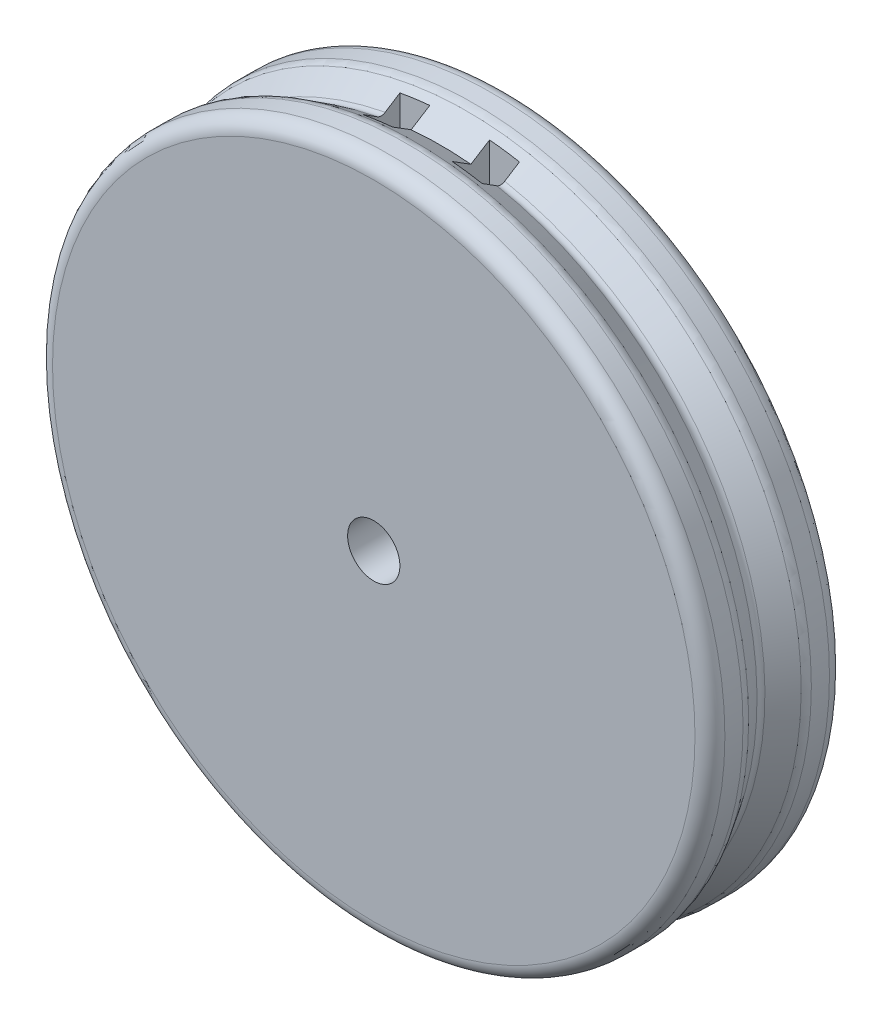
SolidWorks part; units mm, degrees
ref_plane "Front Plane" through (0, 0, 0) normal (0, 0, 1) x (1, 0, 0)
ref_plane "Top Plane" through (0, 0, 0) normal (0, 1, 0) x (1, 0, 0)
ref_plane "Right Plane" through (0, 0, 0) normal (1, 0, 0) x (0, 0, -1)
sketch "Sketch1" plane through (0, 0, 0) normal (0, 0, 1) x (1, 0, 0)
  circle A0 centre (0, 0) radius 42.5
  dimension "D1" = 85
extrude "Boss-Extrude1" add sketch "Sketch1" along normal mid plane 8
sketch "Sketch2" plane through (0, 0, 4) normal (0, 0, 1) x (1, 0, 0)
  circle A0 centre (0, 0) radius 45
  dimension "D1" = 90
extrude "Boss-Extrude2" add sketch "Sketch2" along normal blind 5
sketch "Sketch6" plane through (0, 0, 0) normal (1, 0, 0) x (0, 0, -1)
  line L0 (-4, 45) -> (0, 42.5)
  line L1 (4, 42.5) -> (-4, 42.5) construction
  line L2 (0, 42.5) -> (-4, 42.5)
  line L3 (-4, 42.5) -> (-4, 45)
  line L4 (-30.4204, 0) -> (21.2132, 0) construction
revolve "Revolve1" add sketch "Sketch6" angle 360 about L4
mirror "Mirror1" about plane through (0, 0, 0) normal (0, 0, 1) of "Revolve1", "Boss-Extrude2"
ref_plane "Plane3" through (0, 0, 0) normal (0, 0, 1) x (1, 0, 0)
sketch "Sketch7" plane through (0, 0, 0) normal (0, 0, 1) x (1, 0, 0)
  line L0 (0, 37.5) -> (0, -45) construction
  line L3 (-4, 37.5) -> (-4, 44.8219)
  line L4 (-8, 37.5) -> (-8, 44.2832)
  line L5 (0, 37.5) -> (15.7968, 37.5) construction
  line L6 (4, 37.5) -> (4, 44.8219)
  line L7 (8, 37.5) -> (8, 44.2832)
  arc A2 (-4, 37.5) -> (4, 37.5) centre (0, 37.5) ccw
  arc A3 (-8, 37.5) -> (8, 37.5) centre (0, 37.5) ccw
  circle A6 centre (0, 0) radius 45 construction
  arc A7 (8, 44.2832) -> (4, 44.8219) centre (0, 0) ccw
  arc A8 (-4, 44.8219) -> (-8, 44.2832) centre (0, 0) ccw
  circle A9 centre (0, 0) radius 45 construction
  circle A10 centre (0, 0) radius 45 construction
  dimension "D1" = 4
  dimension "D2" = 8
  dimension "D3" = 37.5
extrude "Cut-Extrude4" cut sketch "Sketch7" against normal mid plane 5
sketch "Sketch4" plane through (0, 0, -9) normal (0, 0, -1) x (-1, 0, 0)
  circle A0 centre (0, 0) radius 3.5
  dimension "D1" = 7
extrude "Cut-Extrude3" cut sketch "Sketch4" against normal through all
fillet "Fillet2" radius 1 1 edges at (0, -42.5, 0)
fillet "Fillet3" radius 2 4 edges at (45, 0, -4) (45, 0, 4) (45, 0, 9) (45, 0, -9)
